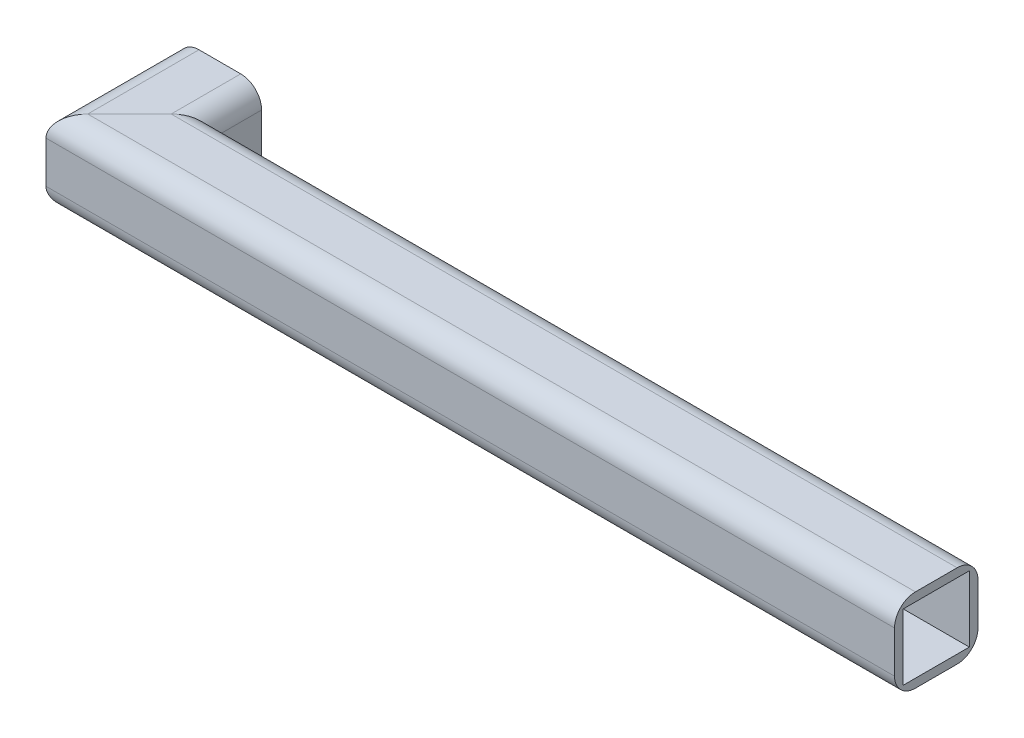
SolidWorks part; units mm, degrees
ref_plane "Front Plane" through (0, 0, 0) normal (0, 0, 1) x (1, 0, 0)
ref_plane "Top Plane" through (0, 0, 0) normal (0, 1, 0) x (1, 0, 0)
ref_plane "Right Plane" through (0, 0, 0) normal (1, 0, 0) x (0, 0, -1)
sketch3d "3DSketch3"
  line L0 (60.325, 60.325, 0) -> (60.325, 60.325, 165.1)
  line L5 (60.325, 60.325, 165.1) -> (1533.525, 60.325, 165.1)
  point P0 (0, 0, 0)
  point P11 (0, 0, 0)
  dimension "D3" = 165.1
  dimension "D4" = 1473.2
sketch "Sketch12" plane through (0, 0, 0) normal (0, 0, 1) x (1, 0, 0)
  line L0 (120.65, 0) -> (120.65, 120.65)
  line L6 (22.225, 136.525) -> (98.425, 136.525)
  line L7 (120.65, 120.65) -> (0, 120.65)
  line L8 (0, 120.65) -> (0, 0)
  line L9 (0, 0) -> (120.65, 0)
  line L10 (-15.875, 98.425) -> (-15.875, 22.225)
  line L11 (22.225, -15.875) -> (98.425, -15.875)
  line L12 (136.525, 98.425) -> (136.525, 22.225)
  line L13 (-15.875, 136.525) -> (136.525, -15.875) construction
  line L14 (-15.875, -15.875) -> (136.525, 136.525) construction
  arc A7 (-15.875, 22.225) -> (22.225, -15.875) centre (22.225, 22.225) ccw
  arc A8 (98.425, -15.875) -> (136.525, 22.225) centre (98.425, 22.225) ccw
  arc A9 (98.425, 136.525) -> (136.525, 98.425) centre (98.425, 98.425) cw
  arc A10 (22.225, 136.525) -> (-15.875, 98.425) centre (22.225, 98.425) ccw
  point P0 (60.325, 60.325)
  point P6 (60.325, 60.325)
  dimension "D3" = 152.4
  dimension "D5" = 38.1
  dimension "D1" = 120.65
  dimension "D2" = 120.65
  dimension "D4" = 152.4
sweep "Sweep1" add profiles "Sketch12" path "3DSketch3"
